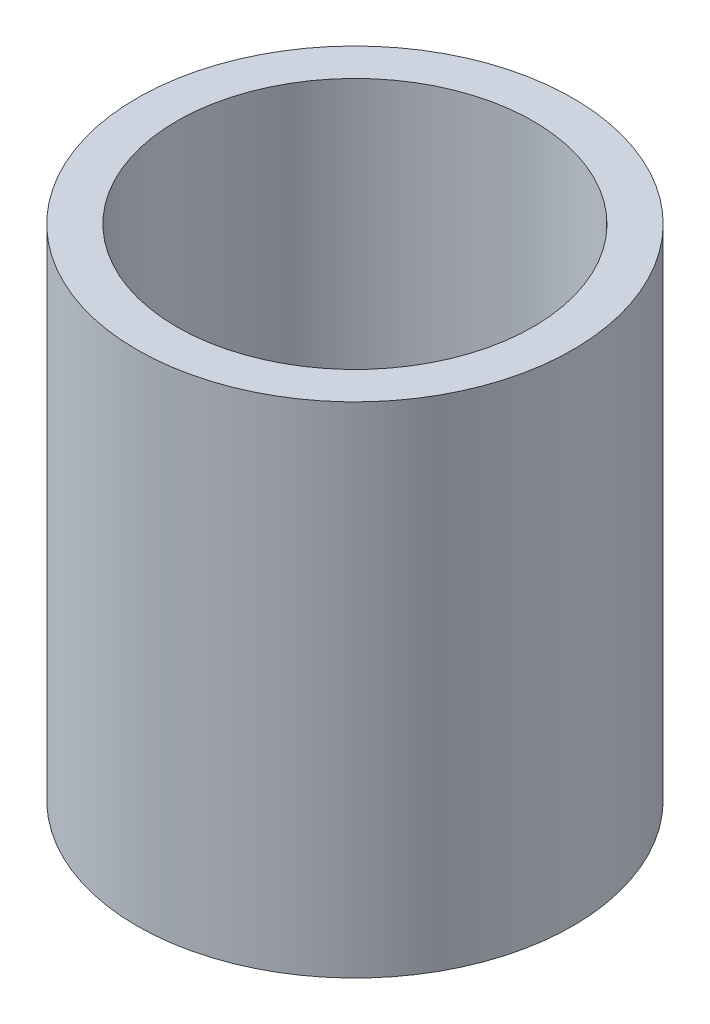
SolidWorks part; units mm, degrees
ref_plane "Front Plane" through (0, 0, 0) normal (0, 0, 1) x (1, 0, 0)
ref_plane "Top Plane" through (0, 0, 0) normal (0, 1, 0) x (1, 0, 0)
ref_plane "Right Plane" through (0, 0, 0) normal (1, 0, 0) x (0, 0, -1)
sketch "Sketch1" plane through (0, 0, 0) normal (0, 1, 0) x (1, 0, 0)
  circle A0 centre (0, 0) radius 15
  dimension "SLEEVE_OD" = 30
extrude "Boss-Extrude1" add sketch "Sketch1" along normal blind 34.3404
sketch "Sketch2" plane through (0, 0, 0) normal (0, 1, 0) x (1, 0, 0)
  circle A0 centre (0, 0) radius 12.2671
  dimension "BORE_D" = 24.5342
extrude "Cut-Extrude1" cut sketch "Sketch2" along normal through all
chamfer "Chamfer1" distance 2.0821 angle 45.201 rebuild error yes
